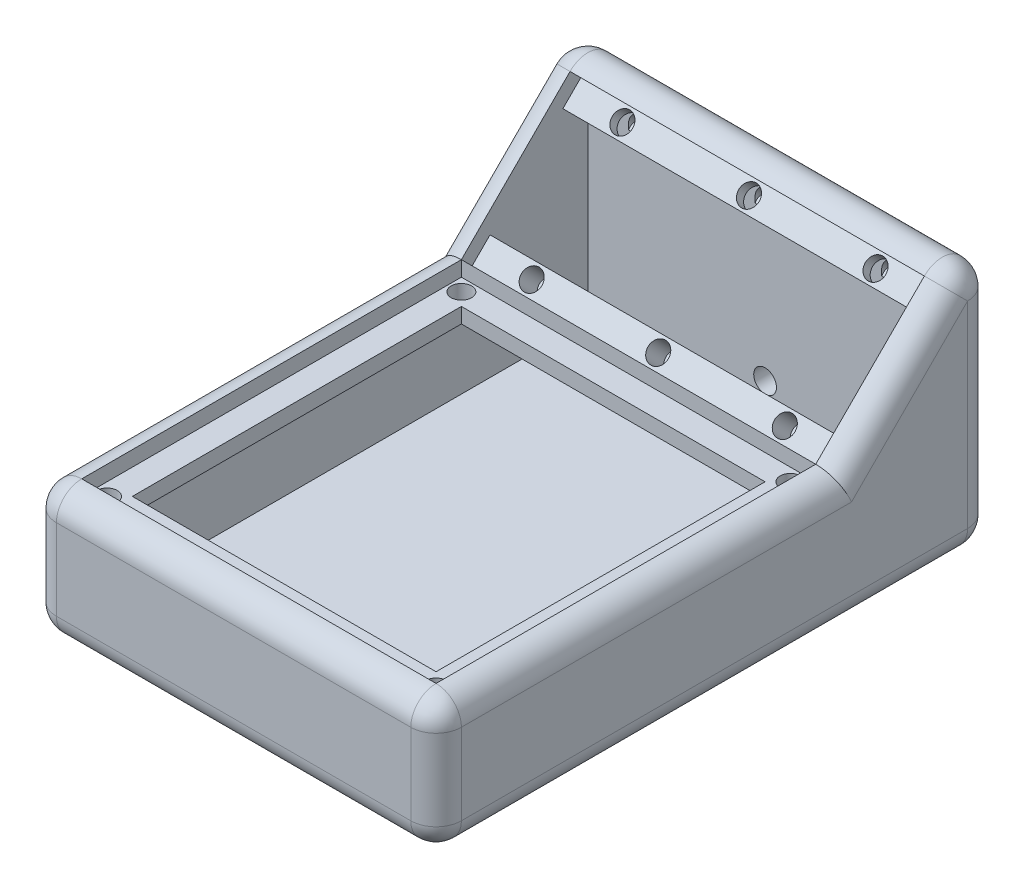
SolidWorks part; units mm, degrees
ref_plane "前基準面" through (0, 0, 0) normal (0, 0, 1) x (1, 0, 0)
ref_plane "上基準面" through (0, 0, 0) normal (0, 1, 0) x (1, 0, 0)
ref_plane "右基準面" through (0, 0, 0) normal (1, 0, 0) x (0, 0, -1)
sketch "草圖1" plane through (0, 0, 0) normal (0, 1, 0) x (1, 0, 0)
  line L1 (-8.2447, 46.2872) -> (71.7553, 46.2872)
  line L2 (-8.2447, 46.2872) -> (-8.2447, -63.7128)
  line L3 (-8.2447, -63.7128) -> (71.7553, -63.7128)
  line L4 (71.7553, 46.2872) -> (71.7553, -63.7128)
  dimension "D1" = 110
  dimension "D2" = 80
extrude "填料-伸長1" add sketch "草圖1" along normal blind 26
ref_plane "平面1" through (0, 0, -41.2872) normal (0, 0, -1) x (-1, 0, 0)
sketch "草圖2" plane through (71.7553, 0, 0) normal (1, 0, 0) x (0, 0, -1)
  line L0 (46.2872, 26) -> (46.2872, 56)
  line L1 (46.2872, 56) -> (16.2872, 26)
  line L2 (-63.7128, 26) -> (46.2872, 26) construction
  line L3 (16.2872, 26) -> (46.2872, 26)
  dimension "D1" = 45
  dimension "D2" = 30
extrude "填料-伸長2" add sketch "草圖2" against normal blind 80
fillet "圓角1" radius 5 14 edges at (31.7553, 26, 63.7128) (71.7553, 26, 23.7128) (71.7553, 41, -31.2872) (-8.2447, 41, -31.2872) (31.7553, 56, -46.2872) (-8.2447, 26, 23.7128) (31.7553, 0, -46.2872) (-8.2447, 28, -46.2872) (-8.2447, 0, 8.7128) (71.7553, 28, -46.2872) (71.7553, 0, 8.7128) (-8.2447, 13, 63.7128) (71.7553, 13, 63.7128) (31.7553, 0, 63.7128)
sketch "草圖4" plane through (0, 0, 0) normal (0, -1, 0) x (1, 0, 0)
  line L0 (-3.2447, -41.2872) -> (66.7553, -41.2872) construction
  line L1 (-3.2447, 58.7128) -> (66.7553, 58.7128)
  line L2 (-3.2447, 58.7128) -> (-3.2447, -41.2872)
  line L3 (-3.2447, -41.2872) -> (66.7553, -41.2872)
  line L4 (66.7553, 58.7128) -> (66.7553, -41.2872)
  line L5 (66.7553, -46.2872) -> (66.7553, -41.2872) construction
extrude "除料-伸長1" cut sketch "草圖4" against normal blind 20
sketch "草圖6" plane through (0, 4.8564, 4.8564) normal (0, 0.7071, 0.7071) x (1, 0, 0)
  line L0 (66.7553, 60.2569) -> (-3.2447, 60.2569) construction
  line L1 (-3.2447, 60.2569) -> (66.7553, 60.2569)
  line L2 (-3.2447, 60.2569) -> (-3.2447, 29.9016)
  line L3 (-3.2447, 29.9016) -> (66.7553, 29.9016)
  line L4 (66.7553, 60.2569) -> (66.7553, 29.9016)
  line L5 (-3.2447, 29.9016) -> (66.7553, 29.9016) construction
  line L6 (-3.2447, 60.2569) -> (-3.2447, 29.9016) construction
  line L7 (66.7553, 29.9016) -> (66.7553, 60.2569) construction
  dimension "D1" = 0
  dimension "D2" = 0
  dimension "D3" = 30.3553
extrude "除料-伸長2" cut sketch "草圖6" against normal up to surface (5 mm away) contours L2 L1 L4 L3 up to plane "平面1"
sketch "草圖8" plane through (0, 26, 0) normal (0, 1, 0) x (1, 0, 0)
  line L0 (-3.2447, 16.2872) -> (66.7553, 16.2872) construction
  line L5 (1.7553, 11.2872) -> (61.7553, 11.2872)
  line L6 (1.7553, 11.2872) -> (1.7553, -53.7128)
  line L7 (1.7553, -53.7128) -> (61.7553, -53.7128)
  line L8 (61.7553, 11.2872) -> (61.7553, -53.7128)
  line L9 (66.7553, -58.7128) -> (66.7553, 16.2872) construction
  line L10 (-3.2447, 16.2872) -> (-3.2447, -58.7128) construction
  line L11 (-3.2447, -58.7128) -> (66.7553, -58.7128) construction
  dimension "D1" = 5
  dimension "D2" = 5
  dimension "D3" = 5
  dimension "D4" = 5
extrude "除料-伸長3" cut sketch "草圖8" against normal blind 20
sketch "草圖9" plane through (0, 21.1436, -21.1436) normal (0, 0.7071, -0.7071) x (1, 0, 0)
  line L1 (-3.2447, 1.6173) -> (66.7553, 1.6173)
  line L2 (-3.2447, 1.6173) -> (-3.2447, -6.868)
  line L3 (-3.2447, -6.868) -> (66.7553, -6.868)
  line L4 (66.7553, 1.6173) -> (66.7553, -6.868)
extrude "填料-伸長3" add sketch "草圖9" along normal blind 5
sketch "草圖11" plane through (0, 42.6081, -42.6081) normal (0, -0.7071, 0.7071) x (1, 0, 0)
  line L1 (-3.2447, 1.868) -> (66.7553, 1.868)
  line L2 (-3.2447, 1.868) -> (-3.2447, 6.868)
  line L3 (-3.2447, 6.868) -> (66.7553, 6.868)
  line L4 (66.7553, 1.868) -> (66.7553, 6.868)
extrude "填料-伸長4" add sketch "草圖11" along normal blind 5
sketch "草圖13" plane through (0, 26, 0) normal (0, 1, 0) x (1, 0, 0)
  line L1 (-3.2447, 16.2872) -> (66.7553, 16.2872)
  line L2 (-3.2447, 16.2872) -> (-3.2447, -58.7128)
  line L3 (-3.2447, -58.7128) -> (66.7553, -58.7128)
  line L4 (66.7553, 16.2872) -> (66.7553, -58.7128)
extrude "除料-伸長4" cut sketch "草圖13" against normal blind 3
sketch "草圖14" plane through (0, 4.8564, 4.8564) normal (0, 0.7071, 0.7071) x (1, 0, 0)
  line L1 (-3.2447, 60.2569) -> (66.7553, 60.2569)
  line L2 (-3.2447, 60.2569) -> (-3.2447, 29.9016)
  line L3 (-3.2447, 29.9016) -> (66.7553, 29.9016)
  line L4 (66.7553, 60.2569) -> (66.7553, 29.9016)
extrude "除料-伸長5" cut sketch "草圖14" against normal blind 3
sketch "草圖15" plane through (0, 0, -41.2872) normal (0, 0, 1) x (1, 0, 0)
  line L1 (-3.2447, 0) -> (66.7553, 0)
  line L2 (-3.2447, 0) -> (-3.2447, 3)
  line L3 (-3.2447, 3) -> (66.7553, 3)
  line L4 (66.7553, 0) -> (66.7553, 3)
  dimension "D1" = 3
extrude "填料-伸長5" add sketch "草圖15" along normal blind 100
sketch "草圖16" plane through (0, 2.7351, 2.7351) normal (0, 0.7071, 0.7071) x (1, 0, 0)
  line L0 (-3.2447, 55.2569) -> (66.7553, 55.2569) construction
  line L1 (-3.2447, 60.2569) -> (-3.2447, 29.9016) construction
  line L2 (66.7553, 55.2569) -> (66.7553, 60.2569) construction
  line L3 (-3.2447, 34.9016) -> (66.7553, 34.9016) construction
  line L4 (-3.2447, 34.9016) -> (-3.2447, 29.9016) construction
  line L5 (66.7553, 29.9016) -> (66.7553, 60.2569) construction
  circle A0 centre (6.7553, 57.7569) radius 2.025
  circle A1 centre (56.7553, 57.7569) radius 2.025
  circle A2 centre (31.7553, 57.7569) radius 2.025
  circle A3 centre (6.7553, 32.4016) radius 2.025
  circle A4 centre (56.7553, 32.4016) radius 2.025
  circle A5 centre (31.7553, 32.4016) radius 2.025
  dimension "D1" = 4.05
  dimension "D4" = 2.5
  dimension "D5" = 10
  dimension "D2" = 2.5
  dimension "D3" = 10
  dimension "D6" = 35
  dimension "D7" = 2.5
  dimension "D8" = 2.5
  dimension "D9" = 10
  dimension "D10" = 2.5
  dimension "D11" = 35
  dimension "D12" = 2.5
  dimension "D13" = 10
extrude "除料-伸長6" cut sketch "草圖16" against normal blind 5
sketch "草圖17" plane through (0, 23, 0) normal (0, 1, 0) x (1, 0, 0)
  line L0 (1.7553, -53.7128) -> (1.7553, 11.2872) construction
  line L1 (1.7553, 11.2872) -> (61.7553, 11.2872) construction
  line L2 (61.7553, -53.7128) -> (1.7553, -53.7128) construction
  line L3 (61.7553, 11.2872) -> (61.7553, -53.7128) construction
  circle A0 centre (-0.7447, 13.7872) radius 2.025
  circle A1 centre (64.2553, -56.2128) radius 2.025
  circle A2 centre (-0.7447, -56.2128) radius 2.025
  circle A3 centre (64.2553, 13.7872) radius 2.025
  point P2 (0, 0)
  point P17 (0, 0)
  dimension "D1" = 4.05
  dimension "D2" = 2.5
  dimension "D3" = 2.5
  dimension "D4" = 2.5
  dimension "D5" = 2.5
  dimension "D6" = 2.5
  dimension "D7" = 2.5
  dimension "D8" = 2.5
  dimension "D9" = 2.5
extrude "除料-伸長7" cut sketch "草圖17" against normal blind 5
sketch "草圖18" plane through (0, 0, -46.2872) normal (0, 0, -1) x (-1, 0, 0)
  line L0 (-66.7553, 5) -> (3.2447, 5) construction
  line L1 (-66.7553, 43.9289) -> (-66.7553, 5) construction
  circle A0 centre (-31.7553, 10.25) radius 2.25
  dimension "D1" = 4.5
  dimension "D2" = 5.25
  dimension "D3" = 35
extrude "除料-伸長8" cut sketch "草圖18" against normal blind 45
